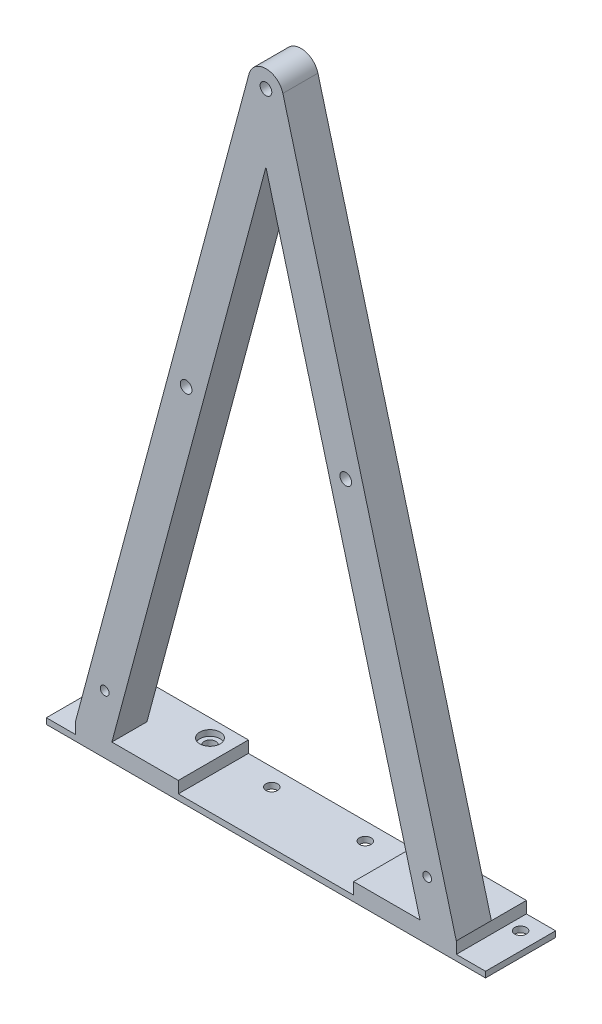
SolidWorks part; units mm, degrees
ref_plane "前视基准面" through (0, 0, 0) normal (0, 0, 1) x (1, 0, 0)
ref_plane "上视基准面" through (0, 0, 0) normal (0, 1, 0) x (1, 0, 0)
ref_plane "右视基准面" through (0, 0, 0) normal (1, 0, 0) x (0, 0, -1)
other "Configuration Table"
sketch "草图1" plane through (0, 0, 0) normal (0, 0, 1) x (1, 0, 0)
  line L3 (0, 0) -> (0, -30) construction
  line L5 (-2.8978, 0.7765) -> (-32.5802, -110)
  line L6 (2.8978, 0.7765) -> (32.5802, -110)
  line L8 (-26.3686, -110) -> (2.8978, -0.7765)
  line L10 (26.3686, -110) -> (-2.8978, -0.7765)
  line L12 (-32.5802, -110) -> (-26.3686, -110)
  line L13 (26.3686, -110) -> (32.5802, -110)
  line L14 (-16.5632, -50.2235) -> (-10.7676, -51.7765) construction
  line L15 (10.7676, -51.7765) -> (16.5632, -50.2235) construction
  circle A0 centre (0, 0) radius 3
  circle A4 centre (13.6654, -51) radius 1
  circle A5 centre (-13.6654, -51) radius 1
  circle A6 centre (0, 0) radius 1
  dimension "D1" = 6
  dimension "D2" = 15
  dimension "D4" = 2
  dimension "D5" = 110
  dimension "D6" = 51
  dimension "D3" = 15
extrude "凸台-拉伸1" add sketch "草图1" along normal blind 6 contours A0 | L6 A0 L8 L10 | L8 L10 A0 L5 | L3 A0 L10 | A0 L3 L8 region at (-15.565, -57.8725, 0) region at (0, 2.9151, 0) region at (15.565, -57.8725, 0) region at (0, -5.5523, 0)
sketch "草图2" plane through (0, 0, 0) normal (0, 0, -1) x (-1, 0, 0)
  circle A0 centre (0, 0) radius 1.75
  circle A1 centre (13.6654, -51) radius 1.75
  circle A2 centre (-13.6654, -51) radius 1.75
  circle A3 centre (-13.6654, -51) radius 1 construction
  circle A4 centre (13.6654, -51) radius 1 construction
  circle A5 centre (0, 0) radius 1 construction
  dimension "D1" = 3.5
extrude "切除-拉伸1" cut sketch "草图2" against normal offset from surface (4 mm away) 2 contours A2 | A1 | A0 up to face at (1, 0, 6)
sketch "草图3" plane through (0, -110, 0) normal (0, -1, 0) x (1, 0, 0)
  line L0 (26.3686, 6) -> (32.5802, 6) construction
  line L1 (37.5802, -6) -> (-37.5802, -6)
  line L2 (37.5802, -6) -> (37.5802, 6)
  line L3 (37.5802, 6) -> (-37.5802, 6)
  line L4 (-37.5802, -6) -> (-37.5802, 6)
  line L5 (26.3686, 0) -> (32.5802, 0) construction
  line L6 (32.5802, 6) -> (32.5802, 0) construction
  line L7 (-32.5802, 6) -> (-32.5802, 0) construction
  dimension "D1" = 6
  dimension "D2" = 5
  dimension "D3" = 5
extrude "凸台-拉伸2" add sketch "草图3" along normal blind 3
sketch "草图4" plane through (0, 0, 6) normal (0, 0, 1) x (1, 0, 0)
  line L0 (37.5802, -113) -> (-37.5802, -113) construction
  line L1 (-30.7046, -103) -> (-24.4929, -103) construction
  line L2 (-2.8978, 0.7765) -> (-32.5802, -110) construction
  line L3 (-26.3686, -110) -> (0, -11.5911) construction
  line L4 (24.4929, -103) -> (30.7046, -103) construction
  line L5 (26.3686, -110) -> (0, -11.5911) construction
  line L6 (2.8978, 0.7765) -> (32.5802, -110) construction
  circle A0 centre (-27.5988, -103) radius 0.75
  circle A1 centre (27.5988, -103) radius 0.75
  dimension "D1" = 1.5
  dimension "D2" = 10
extrude "切除-拉伸2" cut sketch "草图4" against normal blind 3
sketch "草图5" plane through (0, -110, 0) normal (0, 1, 0) x (1, 0, 0)
  line L0 (-37.5802, 6) -> (37.5802, 6) construction
  line L1 (-37.5802, 6) -> (-32.5802, 6)
  line L2 (-37.5802, 6) -> (-37.5802, -6)
  line L3 (-37.5802, -6) -> (-32.5802, -6)
  line L4 (-32.5802, 6) -> (-32.5802, -6)
  line L5 (-37.5802, -6) -> (-37.5802, 6) construction
  line L6 (-2.8978, -6) -> (-32.5802, -6) construction
  line L7 (-32.5802, -6) -> (-37.5802, -6) construction
  line L8 (37.5802, 6) -> (37.5802, -6) construction
  line L9 (37.5802, 6) -> (32.5802, 6)
  line L10 (37.5802, 6) -> (37.5802, -6)
  line L11 (37.5802, -6) -> (32.5802, -6)
  line L12 (32.5802, 6) -> (32.5802, -6)
  line L13 (32.5802, -6) -> (32.5802, 0) construction
  line L14 (2.8978, -6) -> (32.5802, -6) construction
  line L15 (-15, 6) -> (15, 6)
  line L16 (-15, 6) -> (-15, -6)
  line L17 (-15, -6) -> (15, -6)
  line L18 (15, 6) -> (15, -6)
  line L19 (-32.5802, -6) -> (-32.5802, 0) construction
  line L20 (37.5802, -6) -> (32.5802, -6) construction
  line L21 (0, 0) -> (0, 6) construction
  line L22 (2.8978, 0) -> (-2.8978, 0) construction
  dimension "D1" = 30
extrude "切除-拉伸3" cut sketch "草图5" against normal blind 2
sketch "草图6" plane through (0, -110, 0) normal (0, 1, 0) x (1, 0, 0)
  line L0 (-37.5802, 6) -> (-37.5802, -6) construction
  line L1 (-32.5802, 6) -> (-37.5802, 6) construction
  line L2 (37.5802, -6) -> (37.5802, 6) construction
  circle A0 centre (-34.5802, 3) radius 1
  circle A1 centre (-8, 3) radius 1
  circle A2 centre (8, 3) radius 1
  circle A3 centre (34.5802, 3) radius 1
  circle A4 centre (18.5802, 3) radius 1.75
  circle A5 centre (18.5802, 3) radius 1
  circle A6 centre (-18.5802, 3) radius 1.75
  circle A7 centre (-18.5802, 3) radius 1
  dimension "D1" = 2
  dimension "D2" = 3.5
  dimension "D3" = 3
  dimension "D4" = 3
  dimension "D5" = 3
  dimension "D6" = 16
  dimension "D7" = 8
  dimension "D8" = 8
  dimension "D9" = 16
extrude "切除-拉伸4" cut sketch "草图6" against normal through all contours A1 | A0 | A7 | A2 | A5 | A3 region at (-8, -110, -3)
extrude "切除-拉伸5" cut sketch "草图6<3>" against normal blind 1
sketch "草图6<3>" plane through (0, -110, 0) normal (0, 1, 0) x (1, 0, 0) same geometry as "草图6"
